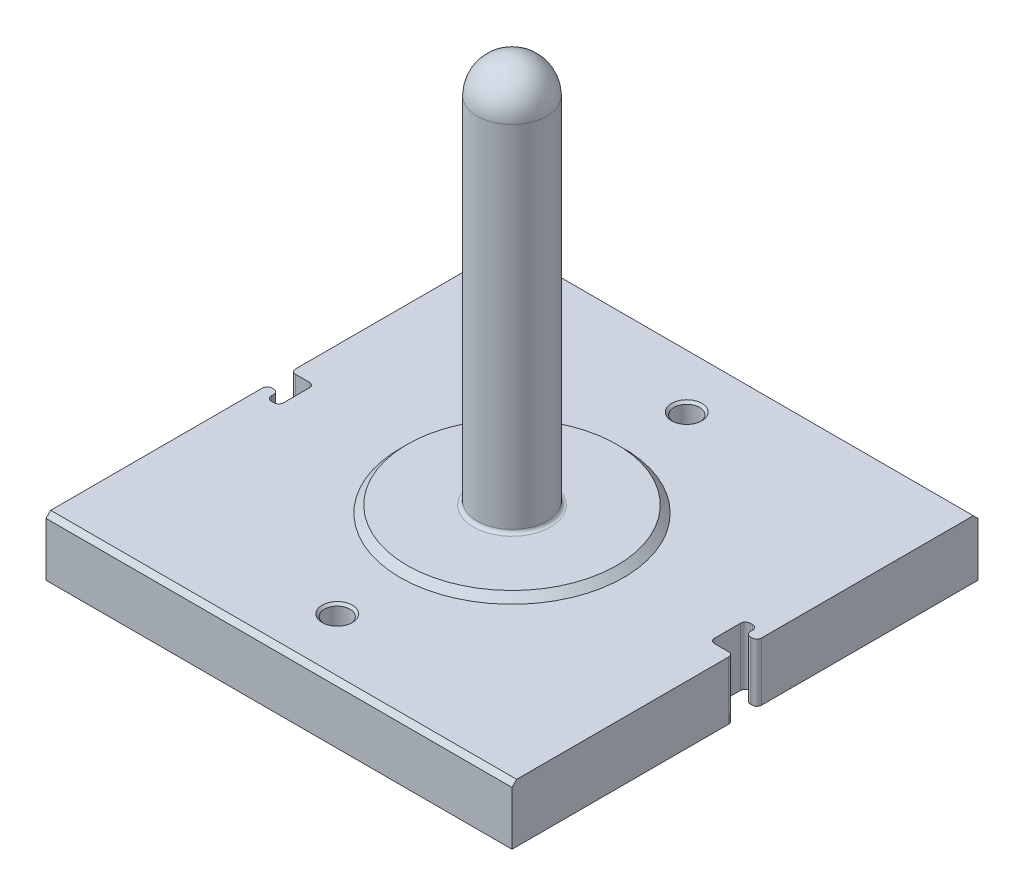
SolidWorks part; units mm, degrees
material "Custom Plastic"
ref_plane "Front Plane" through (0, 0, 0) normal (0, 0, 1) x (1, 0, 0)
ref_plane "Top Plane" through (0, 0, 0) normal (0, 1, 0) x (1, 0, 0)
ref_plane "Right Plane" through (0, 0, 0) normal (1, 0, 0) x (0, 0, -1)
sketch "Sketch1" plane through (0, 0, 0) normal (0, 1, 0) x (1, 0, 0)
  line L1 (-100, 100) -> (100, 100)
  line L2 (-100, 100) -> (-100, -100)
  line L3 (-100, -100) -> (100, -100)
  line L4 (100, 100) -> (100, -100)
  line L5 (-100, 100) -> (100, -100) construction
  line L6 (-100, -100) -> (100, 100) construction
  point P0 (0, 0)
  dimension "D1" = 200
  dimension "D2" = 200
extrude "Boss-Extrude1" add sketch "Sketch1" along normal blind 25
sketch "Sketch2" plane through (0, 25, 0) normal (0, 1, 0) x (1, 0, 0)
  circle A0 centre (0, 0) radius 15
  dimension "D1" = 30
extrude "Boss-Extrude2" add sketch "Sketch2" along normal blind 170
sketch "Sketch3" plane through (0, 0, 0) normal (0, 1, 0) x (1, 0, 0)
  line L0 (-1000, 0) -> (49000, 0) construction
  line L1 (-100, 100) -> (-100, -100) construction
  line L2 (-100, 100) -> (-100, -100) construction
  line L3 (-100, 5.1) -> (-92, 5.1)
  line L4 (-90, 3.1) -> (-90, -8.1)
  line L5 (-92, -10.1) -> (-93.2, -10.1)
  line L6 (-95.2, -8.1) -> (-95.2, -7.1)
  line L7 (-97.2, -5.1) -> (-100, -5.1)
  line L8 (-100, -5.1) -> (-100, 5.1)
  line L9 (100, -100) -> (100, 100) construction
  line L10 (100, -100) -> (100, 100) construction
  line L17 (100, -5.1) -> (92, -5.1)
  line L18 (90, -3.1) -> (90, 8.1)
  line L19 (92, 10.1) -> (93.2, 10.1)
  line L20 (95.2, 8.1) -> (95.2, 7.1)
  line L21 (97.2, 5.1) -> (100, 5.1)
  line L22 (100, 5.1) -> (100, -5.1)
  arc A0 (-92, 5.1) -> (-90, 3.1) centre (-92, 3.1) cw
  arc A1 (-90, -8.1) -> (-92, -10.1) centre (-92, -8.1) cw
  arc A2 (-93.2, -10.1) -> (-95.2, -8.1) centre (-93.2, -8.1) cw
  arc A3 (-95.2, -7.1) -> (-97.2, -5.1) centre (-97.2, -7.1) ccw
  arc A8 (95.2, 7.1) -> (97.2, 5.1) centre (97.2, 7.1) ccw
  arc A9 (93.2, 10.1) -> (95.2, 8.1) centre (93.2, 8.1) cw
  arc A10 (90, 8.1) -> (92, 10.1) centre (92, 8.1) cw
  arc A11 (92, -5.1) -> (90, -3.1) centre (92, -3.1) cw
  point P7 (-100, 0)
  point P15 (-90, 5.1)
  point P18 (-90, -10.1)
  point P21 (-95.2, -10.1)
  point P24 (-95.2, -5.1)
  point P28 (100, 0)
  point P36 (95.2, 5.1)
  point P39 (95.2, 10.1)
  point P42 (90, 10.1)
  point P45 (90, -5.1)
  dimension "D5" = 2
  dimension "D10" = 2
  dimension "D1" = 10.2
  dimension "D2" = 15.2
  dimension "D3" = 4.8
  dimension "D4" = 5.2
  dimension "D6" = 10.2
  dimension "D7" = 15.2
  dimension "D8" = 4.8
  dimension "D9" = 5.2
extrude "Cut-Extrude3" cut sketch "Sketch3" along normal up to next
fillet "Fillet2" radius 2 4 edges at (-100, 12.5, 5.1) (-100, 12.5, -5.1) (100, 12.5, 5.1) (100, 12.5, -5.1)
fillet "Fillet3" radius 15 1 edges at (0, 195, 15)
sketch "Sketch4" plane through (0, 25, 0) normal (0, 1, 0) x (1, 0, 0)
  circle A0 centre (0, 0) radius 45
  dimension "D1" = 90
extrude "Boss-Extrude3" add sketch "Sketch4" along normal blind 3
chamfer "Chamfer1" distance 3 angle 45 1 edges at (0, 25, 45)
fillet "Fillet4" radius 1.5 1 edges at (0, 28, 15)
sketch "Sketch5" plane through (0, 25, 0) normal (0, 1, 0) x (1, 0, 0)
  line L0 (0, -1000) -> (0, 49000) construction
  line L1 (-1000, 0) -> (49000, 0) construction
  circle A0 centre (0, 75) radius 5.5
  circle A1 centre (0, -75) radius 5.5
  dimension "D1" = 11
  dimension "D2" = 150
extrude "Cut-Extrude4" cut sketch "Sketch5" against normal through all
chamfer "Chamfer2" distance 2 angle 45 2 edges at (0, 25, -100) (0, 25, 100)
chamfer "Chamfer3" distance 1 angle 45 2 edges at (0, 25, -69.5) (0, 25, 69.5)
